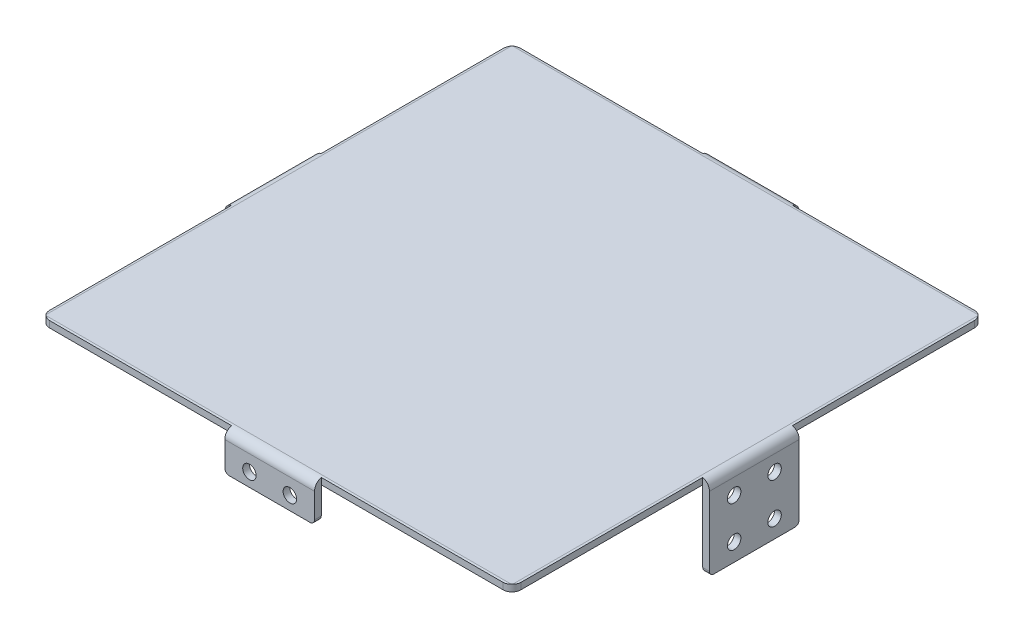
SolidWorks part; units mm, degrees
ref_plane "Front Plane" through (0, 0, 0) normal (0, 0, 1) x (1, 0, 0)
ref_plane "Top Plane" through (0, 0, 0) normal (0, 1, 0) x (1, 0, 0)
ref_plane "Right Plane" through (0, 0, 0) normal (1, 0, 0) x (0, 0, -1)
sketch "Sketch1" plane through (0, 0, 0) normal (0, 1, 0) x (1, 0, 0)
  line L1 (-52.5, -52.5) -> (52.5, -52.5)
  line L2 (-52.5, -52.5) -> (-52.5, 52.5)
  line L3 (-52.5, 52.5) -> (52.5, 52.5)
  line L4 (52.5, -52.5) -> (52.5, 52.5)
  line L5 (-52.5, -52.5) -> (52.5, 52.5) construction
  line L6 (-52.5, 52.5) -> (52.5, -52.5) construction
  point P0 (0, 0)
  dimension "D1" = 105
extrude "Boss-Extrude1" add sketch "Sketch1" along normal blind 1.5 contours L2 L1 L4 L3
sketch "Sketch2" plane through (0, 1.5, 0) normal (0, 1, 0) x (1, 0, 0)
  line L0 (-52.5, 52.5) -> (52.5, 52.5) construction
  line L1 (-10, 52.5) -> (10, 52.5)
  line L2 (-10, 52.5) -> (-10, 54)
  line L3 (-10, 54) -> (10, 54)
  line L4 (10, 52.5) -> (10, 54)
  line L5 (-52.5, -52.5) -> (-52.5, 52.5) construction
  line L6 (-52.5, 0) -> (52.5, 0) construction
  line L7 (52.5, -52.5) -> (52.5, 52.5) construction
  line L8 (-10, -54) -> (10, -54)
  line L9 (10, -52.5) -> (10, -54)
  line L10 (-10, -52.5) -> (10, -52.5)
  line L11 (-10, -52.5) -> (-10, -54)
  point P13 (0, 0)
  dimension "D1" = 20
  dimension "D2" = 42.5
  dimension "D3" = 1.5
sketch "Sketch3" plane through (0, 1.5, 0) normal (0, 1, 0) x (1, 0, 0)
  line L0 (0, 52.5) -> (0, -52.5) construction
  line L1 (-10, 52.5) -> (10, 52.5) construction
  line L2 (-10, -52.5) -> (10, -52.5) construction
  line L3 (52.5, -52.5) -> (52.5, 52.5) construction
  line L4 (52.5, -10) -> (54, -10)
  line L5 (52.5, -10) -> (52.5, 10)
  line L6 (52.5, 10) -> (54, 10)
  line L7 (54, -10) -> (54, 10)
  line L8 (-52.5, 52.5) -> (52.5, 52.5) construction
  line L9 (-52.5, 10) -> (-54, 10)
  line L10 (-54, -10) -> (-54, 10)
  line L11 (-52.5, -10) -> (-54, -10)
  line L12 (-52.5, -10) -> (-52.5, 10)
  dimension "D1" = 20
  dimension "D2" = 42.5
  dimension "D3" = 1.5
extrude "Boss-Extrude2" add sketch "Sketch2" against normal blind 8.5
extrude "Boss-Extrude3" add sketch "Sketch3" against normal blind 18.45
sketch "Sketch4" plane through (0, 0, 54) normal (0, 0, 1) x (1, 0, 0)
  line L0 (0, 1.5) -> (0, -7) construction
  line L1 (-10, 1.5) -> (10, 1.5) construction
  line L2 (-10, -7) -> (10, -7) construction
  line L3 (-52.5, 0) -> (-10, 0) construction
  circle A0 centre (-4.5, -4) radius 1.5
  circle A1 centre (4.5, -4) radius 1.5
  dimension "D1" = 3
  dimension "D2" = 4.5
  dimension "D3" = 4
extrude "Cut-Extrude1" cut sketch "Sketch4" against normal through all
sketch "Sketch5" plane through (54, 0, 0) normal (1, 0, 0) x (0, 0, -1)
  line L1 (-10, -16.95) -> (-10, 1.5) construction
  line L2 (0, 1.5) -> (0, -16.95) construction
  line L3 (-10, 1.5) -> (10, 1.5) construction
  line L4 (-10, -16.95) -> (10, -16.95) construction
  line L5 (10, -8.5) -> (-10, -8.5) construction
  line L6 (10, -16.95) -> (10, 1.5) construction
  circle A0 centre (-4.5, -4) radius 1.5
  circle A1 centre (4.5, -4) radius 1.5
  circle A2 centre (4.5, -13) radius 1.5
  circle A3 centre (-4.5, -13) radius 1.5
  dimension "D1" = 3
  dimension "D2" = 4.5
  dimension "D3" = 4.5
  dimension "D4" = 8.45
extrude "Cut-Extrude2" cut sketch "Sketch5" against normal through all
fillet "Fillet1" radius 1 8 edges at (-10, -7, -53.25) (10, -7, -53.25) (10, -7, 53.25) (-10, -7, 53.25) (53.25, -16.95, 10) (53.25, -16.95, -10) (-53.25, -16.95, -10) (-53.25, -16.95, 10)
fillet "Fillet2" radius 2 4 edges at (-54, 1.5, 0) (54, 1.5, 0) (0, 1.5, -54) (0, 1.5, 54)
fillet "Fillet3" radius 2 4 edges at (52.5, 0.7182, -52.5) (52.5, 0.7182, 52.5) (-52.5, 0.7182, 52.5) (-52.5, 0.7182, -52.5)
